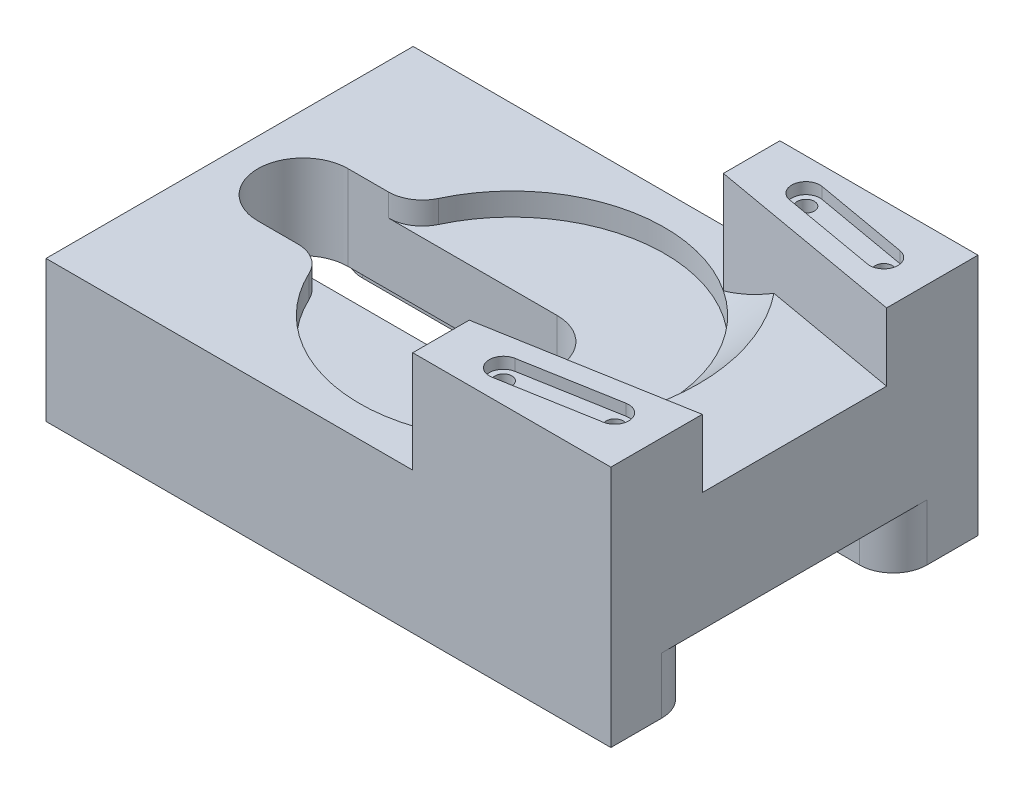
SolidWorks part; units mm, degrees
material "1.0037 (S235JR)"
ref_plane "Front Plane" through (0, 0, 0) normal (0, 0, 1) x (1, 0, 0)
ref_plane "Top Plane" through (0, 0, 0) normal (0, 1, 0) x (1, 0, 0)
ref_plane "Right Plane" through (0, 0, 0) normal (1, 0, 0) x (0, 0, -1)
sketch "Sketch3" plane through (0, 0, 0) normal (0, 1, 0) x (1, 0, 0)
  line L1 (0, 0) -> (100, 0)
  line L2 (0, 0) -> (0, 65)
  line L3 (0, 65) -> (100, 65)
  line L4 (100, 0) -> (100, 65)
  dimension "D1" = 65
  dimension "D2" = 100
extrude "Boss-Extrude1" add sketch "Sketch3" along normal blind 25
sketch "Sketch5" plane through (0, 0, 0) normal (0, -1, 0) x (1, 0, 0)
  line L0 (0, 0) -> (0, -65) construction
  line L1 (100, 0) -> (100, -65) construction
  line L2 (0, -50) -> (100, -50)
  line L3 (0, -50) -> (0, -15)
  line L4 (0, -15) -> (100, -15)
  line L5 (100, -50) -> (100, -15)
  point P10 (0, -32.5)
  point P11 (0, -32.5)
  dimension "D1" = 35
extrude "Cut-Extrude1" cut sketch "Sketch5" against normal blind 10
fillet "Fillet5" radius 6 4 edges at (100, 5, -15) (100, 5, -50) (0, 5, -15) (0, 5, -50) tangent propagation no
sketch "Sketch6" plane through (0, 25, 0) normal (0, 1, 0) x (1, 0, 0)
  line L0 (0, 32.5) -> (100, 32.5) construction
  line L3 (100, 0) -> (100, 65) construction
  line L4 (13, 32.5) -> (50, 32.5) construction
  line L5 (13, 40.5) -> (50, 40.5)
  line L6 (13, 24.5) -> (50, 24.5)
  line L7 (0, 65) -> (0, 0) construction
  arc A0 (13, 40.5) -> (13, 24.5) centre (13, 32.5) ccw
  arc A1 (50, 24.5) -> (50, 40.5) centre (50, 32.5) ccw
  point P3 (0, 32.5)
  point P7 (31.5, 32.5)
  dimension "D1" = 8
  dimension "D2" = 13
  dimension "D3" = 37
extrude "Cut-Extrude2" cut sketch "Sketch6" against normal through all
sketch "Sketch7" plane through (0, 25, 0) normal (0, 1, 0) x (1, 0, 0)
  circle A0 centre (50, 32.5) radius 27
  dimension "D1" = 54
extrude "Cut-Extrude3" cut sketch "Sketch7" against normal blind 4
fillet "Fillet6" radius 6 2 edges at (24.2124, 23, -24.5) (24.2124, 23, -40.5)
sketch "Sketch8" plane through (0, 25, 0) normal (0, 1, 0) x (1, 0, 0)
  line L0 (100, 65) -> (64.9248, 65)
  line L2 (64.9248, 65) -> (64.9248, 55)
  line L3 (100, 65) -> (100, 0)
  line L4 (100, 0) -> (64.9248, 0)
  line L6 (64.9248, 0) -> (64.9248, 10)
  arc A0 (25.5502, 21.0455) -> (25.5502, 43.9545) centre (50, 32.5) ccw construction
  arc A1 (64.9248, 10) -> (64.9248, 55) centre (50, 32.5) ccw
  dimension "D2" = 45
extrude "Boss-Extrude2" add sketch "Sketch8" along normal blind 18
sketch "Sketch9" plane through (0, 43, 0) normal (0, 1, 0) x (1, 0, 0)
  line L0 (64.9248, 55) -> (100, 48.8153)
  line L1 (100, 48.8153) -> (100, 16.1847)
  line L2 (100, 16.1847) -> (64.9248, 10)
  line L3 (100, 0) -> (100, 65) construction
  arc A0 (64.9248, 10) -> (64.9248, 55) centre (50, 32.5) ccw construction
  arc A1 (64.9248, 10) -> (64.9248, 55) centre (50, 32.5) ccw
  dimension "D1" = 80
  dimension "D2" = 80
  dimension "D3" = 45
extrude "Cut-Extrude4" cut sketch "Sketch9" against normal blind 12
fillet "Chamfer1" radius 6 1 edges at (77, 31, -32.5) type face fillet profile chamfer first side face at (85.4812, 31, -32.5) second side face at (52.5456, 25.5, -32.5)
sketch "Sketch10" plane through (0, 43, 0) normal (0, 1, 0) x (1, 0, 0)
  line L0 (75.2583, 59.2705) -> (92, 56.3185) construction
  line L1 (75.6924, 61.7325) -> (92.4341, 58.7805)
  line L2 (74.8241, 56.8085) -> (91.5659, 53.8565)
  line L3 (100, 48.8153) -> (75.7938, 53.0835) construction
  line L4 (100, 48.8153) -> (100, 65) construction
  line L5 (100, 48.8153) -> (64.9248, 55) construction
  arc A0 (75.6924, 61.7325) -> (74.8241, 56.8085) centre (75.2583, 59.2705) ccw
  arc A1 (91.5659, 53.8565) -> (92.4341, 58.7805) centre (92, 56.3185) ccw
  point P2 (83.6291, 57.7945)
  dimension "D1" = 2.5
  dimension "D2" = 8
  dimension "D3" = 6
  dimension "D4" = 17
extrude "Cut-Extrude5" cut sketch "Sketch10" against normal blind 2
sketch "Sketch11" plane through (0, 41, 0) normal (0, 1, 0) x (1, 0, 0)
  circle A0 centre (92, 56.3185) radius 1.5
  circle A1 centre (75.2583, 59.2705) radius 1.5
  dimension "D1" = 3
  dimension "D2" = 3
extrude "Cut-Extrude6" cut sketch "Sketch11" against normal through all
ref_plane "Plane4" through (0, 0, -32.5) normal (0, 0, 1) x (1, 0, 0)
mirror "Mirror1" about plane through (0, 0, -32.5) normal (0, 0, 1) of "Cut-Extrude6", "Cut-Extrude5"
